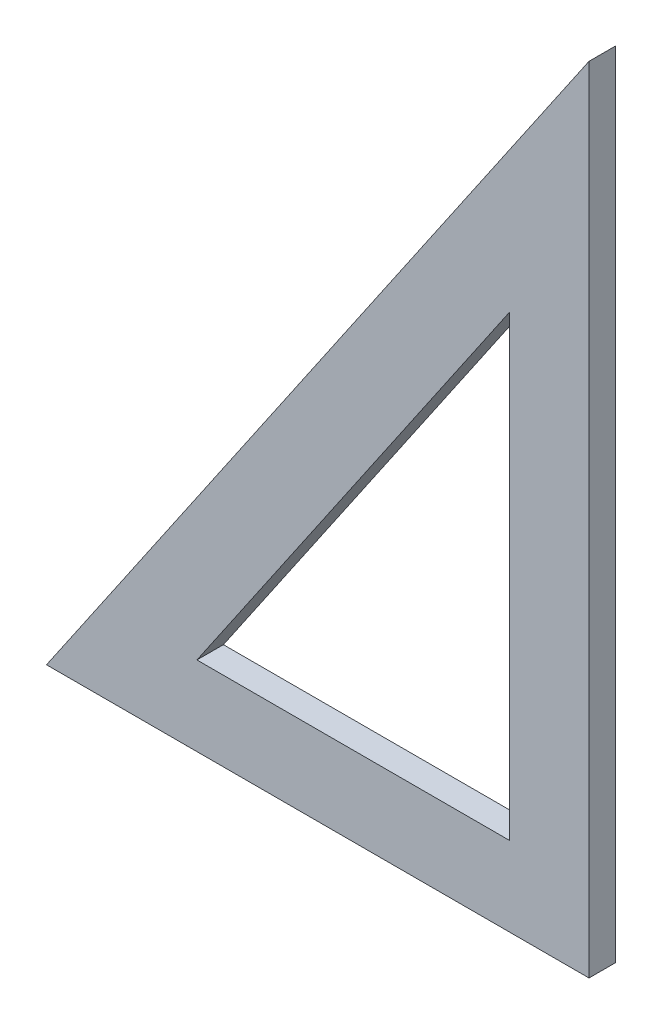
SolidWorks part; units mm, degrees
ref_plane "Front Plane" through (0, 0, 0) normal (0, 0, 1) x (1, 0, 0)
ref_plane "Top Plane" through (0, 0, 0) normal (0, 1, 0) x (1, 0, 0)
ref_plane "Right Plane" through (0, 0, 0) normal (1, 0, 0) x (0, 0, -1)
sketch "Sketch1" plane through (0, 0, 0) normal (0, 0, 1) x (1, 0, 0)
  line L0 (69.85, 285.75) -> (69.85, 95.25)
  line L1 (69.85, 158.75) -> (69.85, 209.55) construction
  line L2 (69.85, 95.25) -> (-60.325, 95.25)
  line L3 (-60.325, 95.25) -> (69.85, 285.75)
  dimension "D1" = 190.5
  dimension "D2" = 130.175
extrude "Boss-Extrude1" add sketch "Sketch1" along normal mid plane 6.35
sketch "Sketch2" plane through (0, 0, 3.175) normal (0, 0, 1) x (1, 0, 0)
  line L9 (-24.2346, 114.3) -> (50.8, 114.3)
  line L10 (50.8, 114.3) -> (50.8, 224.1068)
  line L11 (50.8, 224.1068) -> (-24.2346, 114.3)
  line L12 (-24.2346, 114.3) -> (50.8, 114.3)
  line L13 (50.8, 114.3) -> (50.8, 224.1068)
  line L14 (50.8, 224.1068) -> (-24.2346, 114.3)
  dimension "D1" = 19.05
extrude "Cut-Extrude1" cut sketch "Sketch2" against normal through all
